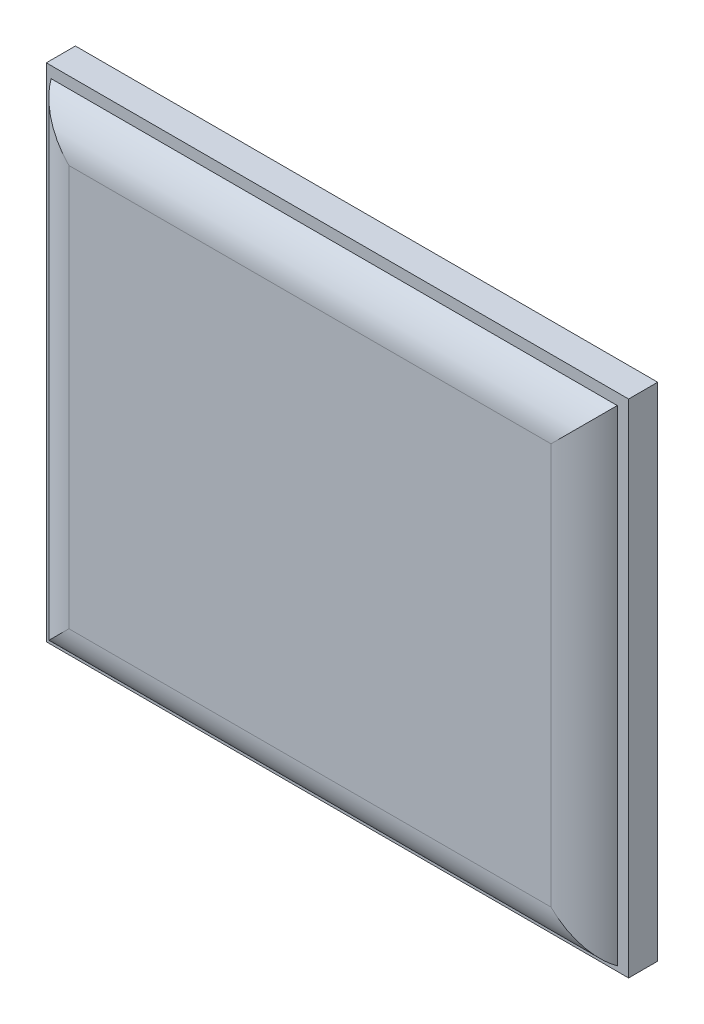
SolidWorks part; units mm, degrees
ref_plane "Спереди" through (0, 0, 0) normal (0, 0, 1) x (1, 0, 0)
ref_plane "Сверху" through (0, 0, 0) normal (0, 1, 0) x (1, 0, 0)
ref_plane "Справа" through (0, 0, 0) normal (1, 0, 0) x (0, 0, -1)
sketch "Sketch2" plane through (0, 0, 0) normal (0, 0, 1) x (1, 0, 0)
  line L1 (35, -30) -> (-35, -30)
  line L2 (35, -30) -> (35, 30)
  line L3 (35, 30) -> (-35, 30)
  line L4 (-35, -30) -> (-35, 30)
  line L5 (35, -30) -> (-35, 30) construction
  line L6 (35, 30) -> (-35, -30) construction
  point P0 (0, 0)
  dimension "D1" = 70
  dimension "D2" = 60
extrude "Boss-Extrude1" add sketch "Sketch2" along normal blind 3
sketch "Sketch3" plane through (0, 0, 0) normal (0, 0, -1) x (-1, 0, 0)
  line L1 (26.8, 19.8) -> (-26.8, 19.8) construction
  line L2 (26.8, 19.8) -> (26.8, -19.8)
  line L3 (26.8, -19.8) -> (-26.8, -19.8) construction
  line L4 (-26.8, 19.8) -> (-26.8, -19.8)
  line L5 (26.8, 19.8) -> (-26.8, -19.8) construction
  line L6 (26.8, -19.8) -> (-26.8, 19.8) construction
  line L8 (-26.8, 19.8) -> (-16.8, 19.8)
  line L9 (-16.8, 19.8) -> (-16.8, -19.8)
  line L10 (-16.8, -19.8) -> (-26.8, -19.8)
  line L11 (26.8, 19.8) -> (16.8, 19.8)
  line L12 (16.8, 19.8) -> (16.8, -19.8)
  line L13 (16.8, -19.8) -> (26.8, -19.8)
  point P0 (0, 0)
  dimension "D1" = 39.6
  dimension "D2" = 53.6
  dimension "D3" = 10
extrude "Boss-Extrude2" add sketch "Sketch3" along normal blind 4
fillet "Fillet1" radius 6 4 edges at (0, 30, 3) (35, 0, 3) (0, -30, 3) (-35, 0, 3)
chamfer "Chamfer1" distance 1 angle 30 4 edges at (-21.8, -19.8, -4) (21.8, -19.8, -4) (-21.8, 19.8, -4) (21.8, 19.8, -4) first distance on face at (-21.8, -19.8, -2) first distance on face at (21.8, -19.8, -2) first distance on face at (-21.8, 19.8, -2) first distance on face at (21.8, 19.8, -2)
sketch "Sketch4" plane through (0, 0, 0) normal (0, 0, -1) x (-1, 0, 0)
  line L0 (-35, 30) -> (35, 30) construction
  line L1 (36, -31) -> (-36, -31)
  line L2 (36, -31) -> (36, 31)
  line L3 (36, 31) -> (-36, 31)
  line L4 (-36, -31) -> (-36, 31)
  line L5 (36, -31) -> (-36, 31) construction
  line L6 (36, 31) -> (-36, -31) construction
  line L7 (32, -27) -> (-32, -27)
  line L8 (32, -27) -> (32, 27)
  line L9 (32, 27) -> (-32, 27)
  line L10 (-32, -27) -> (-32, 27)
  line L11 (32, -27) -> (-32, 27) construction
  line L12 (32, 27) -> (-32, -27) construction
  line L13 (-35, -30) -> (-35, 30) construction
  point P0 (0, 0)
  point P6 (0, 0)
  dimension "D1" = 3
  dimension "D2" = 3
  dimension "D3" = 4
  dimension "D4" = 4
extrude "Boss-Extrude3" add sketch "Sketch4" along normal up to surface (4 mm away) from offset 0.4 separate body up to face at (21.8, 0, -4)
